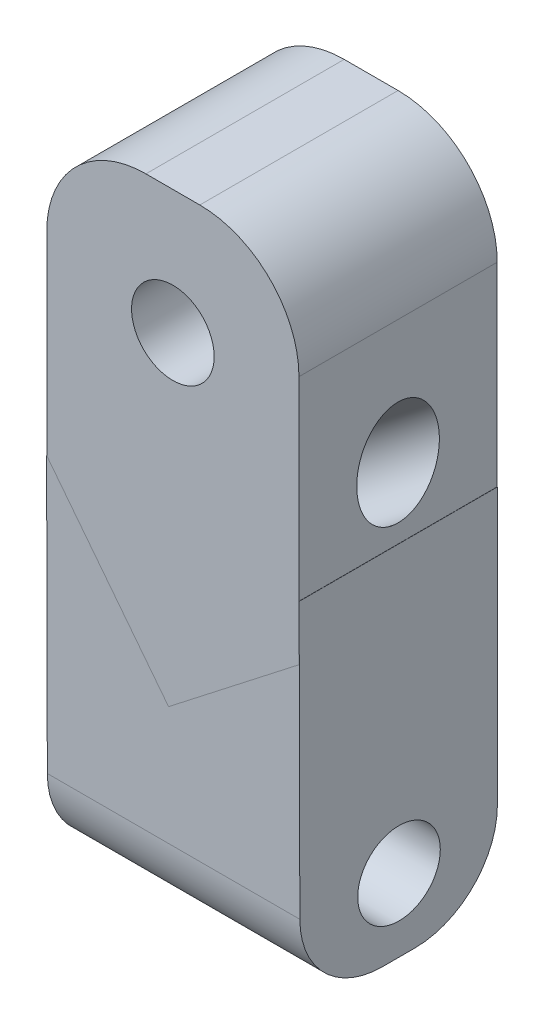
SolidWorks part; units mm, degrees
ref_plane "Front Plane" through (0, 0, 0) normal (0, 0, 1) x (1, 0, 0)
ref_plane "Top Plane" through (0, 0, 0) normal (0, 1, 0) x (1, 0, 0)
ref_plane "Right Plane" through (0, 0, 0) normal (1, 0, 0) x (0, 0, -1)
sketch "Sketch3" plane through (0, 0, 0) normal (0, 0, 1) x (1, 0, 0)
  line L3 (0, 0) -> (58.4671, 45.5154)
  line L4 (58.4671, 45.5154) -> (58.4671, 0)
  line L5 (58.4671, 0) -> (0, 0)
  dimension "D1" = 37.9
ref_plane "Plane1" through (0, 0, 0) normal (0.7891, 0.6143, 0) x (0, 0, -1)
sketch "Sketch5" plane through (0, 0, 0) normal (0.7891, 0.6143, 0) x (0, 0, -1)
  line L1 (-30, -30) -> (30, -30)
  line L2 (-30, -30) -> (-30, 30)
  line L3 (-30, 30) -> (30, 30)
  line L4 (30, -30) -> (30, 30)
  line L5 (-30, -30) -> (30, 30) construction
  line L6 (-30, 30) -> (30, -30) construction
  circle A0 centre (0, 0) radius 12.5
  point P0 (0, 0)
  dimension "D3" = 25
  dimension "D1" = 60
  dimension "D2" = 60
extrude "Boss-Extrude3" add sketch "Sketch5" along normal mid plane 50
sketch "Sketch9" plane through (0, 0, 0) normal (0, 0, 1) x (1, 0, 0)
  line L0 (38.1557, -8.3154) -> (38.1557, 67.1791)
  line L1 (8.1557, 97.1791) -> (-8.1557, 97.1791)
  line L2 (-38.1557, 67.1791) -> (-38.1557, 8.3154)
  line L3 (-38.1557, 8.3154) -> (38.1557, -8.3154)
  circle A0 centre (0, 59.5973) radius 12.5
  arc A1 (8.1557, 97.1791) -> (38.1557, 67.1791) centre (8.1557, 67.1791) cw
  arc A2 (-8.1557, 97.1791) -> (-38.1557, 67.1791) centre (-8.1557, 67.1791) ccw
  dimension "D1" = 25
  dimension "D2" = 30
extrude "Boss-Extrude5" add sketch "Sketch9" along normal mid plane 60
sketch "Sketch10" plane through (0, 0, 0) normal (1, 0, 0) x (0, 0, -1)
  line L1 (-4.7826, -100.0505) -> (5, -100.0505)
  line L4 (30, 8.3154) -> (30, -75.0505)
  line L5 (-30, 8.3154) -> (-29.7825, -75.1157)
  line L6 (-30, 8.3154) -> (30, 8.3154)
  circle A0 centre (0.2253, -78.0505) radius 12.5
  arc A1 (30, -75.0505) -> (5, -100.0505) centre (5, -75.0505) cw
  arc A2 (-29.7825, -75.1157) -> (-4.7826, -100.0505) centre (-4.7826, -75.0505) ccw
  dimension "D1" = 25
  dimension "D2" = 30
  dimension "D3" = 22
  dimension "D4" = 25
extrude "Boss-Extrude6" add sketch "Sketch10" along normal mid plane 76.42
extrude "Cut-Extrude2" cut sketch "Sketch5<2>" against normal mid plane 230 contours A0
sketch "Sketch5<2>" plane through (0, 0, 0) normal (0.7891, 0.6143, 0) x (0, 0, -1) same geometry as "Sketch5"
